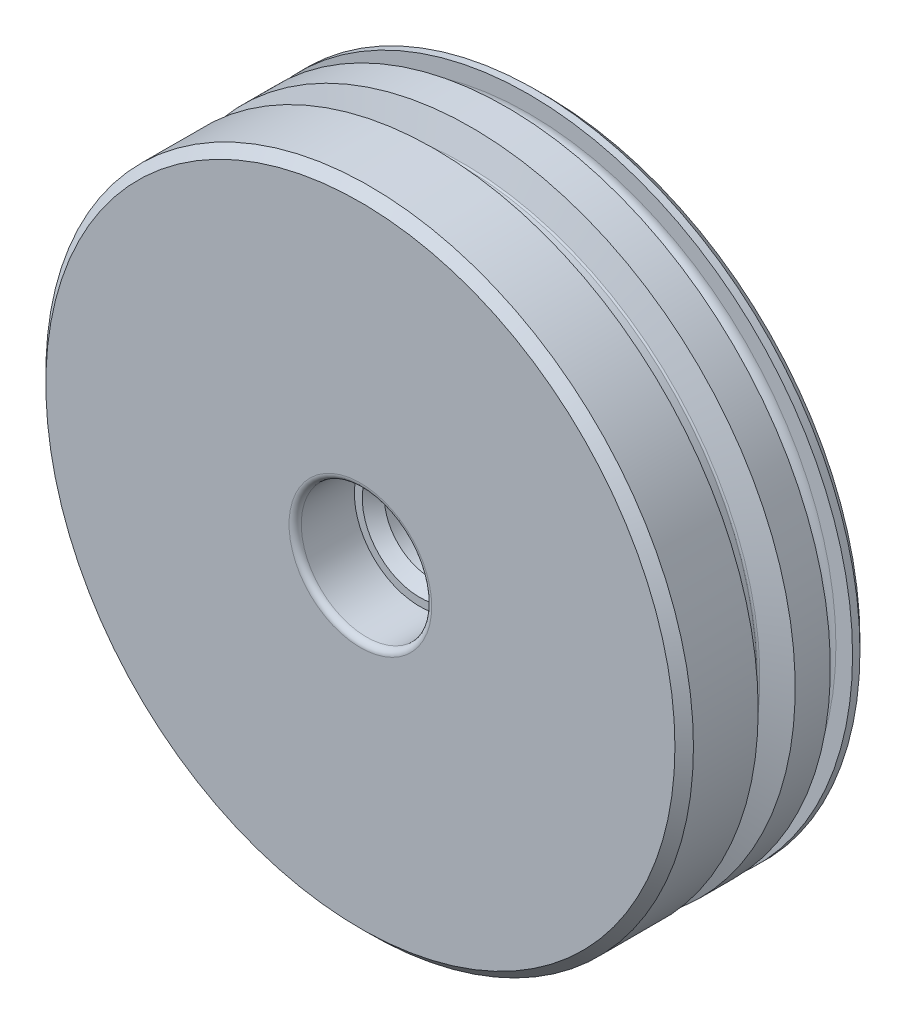
SolidWorks part; units mm, degrees
material "Delrin 2700 NC010, Low Viscosity Acetal Copolymer (SS)"
ref_plane "Front Plane" through (0, 0, 0) normal (0, 0, 1) x (1, 0, 0)
ref_plane "Top Plane" through (0, 0, 0) normal (0, 1, 0) x (1, 0, 0)
ref_plane "Right Plane" through (0, 0, 0) normal (1, 0, 0) x (0, 0, -1)
sketch "Sketch1" plane through (0, 0, 0) normal (0, 0, 1) x (1, 0, 0)
  circle A0 centre (0, 0) radius 17.5
  dimension "D1" = 35
extrude "Boss-Extrude1" add sketch "Sketch1" along normal blind 5 and the other way blind 5
sketch "Sketch3" plane through (0, 0, 0) normal (1, 0, 0) x (0, 0, -1)
  line L0 (0, 19.25) -> (0, -19.25) construction
  line L2 (-1, 17.5) -> (-0.5228, 16.0684)
  line L4 (-0.4279, 16) -> (0.4279, 16)
  line L5 (-1, 17.5) -> (1, 17.5)
  line L6 (0.5228, 16.0684) -> (1, 17.5)
  arc A0 (0.4279, 16) -> (0.5228, 16.0684) centre (0.4279, 16.1) ccw
  arc A1 (-0.4279, 16) -> (-0.5228, 16.0684) centre (-0.4279, 16.1) cw
  point P1 (0, 16)
  point P5 (0, 17.5)
  point P10 (0.5, 16)
  point P14 (-0.5, 16)
  dimension "D1" = 1
  dimension "D4" = 0.1
  dimension "D2" = 2
  dimension "D3" = 1.5
ref_axis "Axis1" through (0, 0, -0.35) along (0, 0, 1)
revolve "Cut-Revolve1" cut sketch "Sketch3" angle 360 about axis through (0, 0, -0.35) along (0, 0, 1)
sketch "Sketch2" plane through (0, 0, 5) normal (0, 0, 1) x (1, 0, 0)
  circle A0 centre (0, 0) radius 3.525
  dimension "D1" = 7.05
extrude "Cut-Extrude1" cut sketch "Sketch2" against normal blind 3.2
chamfer "Chamfer1" distance 0.5 angle 45 2 edges at (17.5, 0, 5) (17.5, 0, -5)
sketch "Sketch4" plane through (0, 0, 1.8) normal (0, 0, 1) x (1, 0, 0)
  circle A0 centre (0, 0) radius 2.5
  dimension "D1" = 5
extrude "Cut-Extrude2" cut sketch "Sketch4" against normal through all
ref_axis "Axis2" through (0, 19.25, 5) along (0, -1, 0)
chamfer "Chamfer2" distance 0.6 angle 45 1 edges at (2.5, 0, 1.8)
mirror "Mirror2" about plane through (0, 0, 0) normal (0, 0, 1) of "Chamfer2", "Cut-Extrude1"
ref_plane "Plane4" through (0, 17.5, 0) normal (0, 1, 0) x (1, 0, 0)
sketch "Sketch7" plane through (0, 0, 0) normal (1, 0, 0) x (0, 0, -1)
  line L5 (4.5, 17.5) -> (4.5, -17.5) construction
  line L7 (2.9, 16.6) -> (2.9, 17.5)
  line L8 (2.9, 17.5) -> (4.1, 17.5)
  line L9 (4.1, 17.5) -> (4.1, 16.6)
  line L10 (3.5, 16) -> (4.2963, 16) construction
  arc A0 (2.9, 16.6) -> (4.1, 16.6) centre (3.5, 16.6) ccw
  dimension "D1" = 1.2
  dimension "D3" = 1.5
  dimension "D2" = 1
revolve "Cut-Revolve3" cut sketch "Sketch7" angle 360 about axis through (0, 0, -0.35) along (0, 0, 1)
fillet "Fillet1" radius 0.33 2 edges at (3.525, 0, 5) (3.525, 0, -5)
sketch "Sketch9" plane through (0, 0, -5) normal (0, 0, -1) x (-1, 0, 0)
  line L0 (-4.4, 1.6) -> (-7.6, 1.6)
  line L1 (7.6, 1.6) -> (4.4, 1.6)
  line L2 (7.6, 1.6) -> (7.6, -1.6)
  line L3 (7.6, -1.6) -> (4.4, -1.6)
  line L4 (4.4, 1.6) -> (4.4, -1.6)
  line L5 (7.6, 1.6) -> (4.4, -1.6) construction
  line L6 (7.6, -1.6) -> (4.4, 1.6) construction
  line L7 (-4.4, 1.6) -> (-4.4, -1.6)
  line L8 (-4.4, -1.6) -> (-7.6, -1.6)
  line L9 (-7.6, 1.6) -> (-7.6, -1.6)
  line L10 (-4.4, 1.6) -> (-7.6, -1.6) construction
  line L11 (-4.4, -1.6) -> (-7.6, 1.6) construction
  line L13 (0, 0) -> (4.4, 0) construction
  line L14 (0, 0) -> (-4.4, 0) construction
  point P0 (6, 0)
  point P5 (-6, 0)
  dimension "D1" = 3.2
  dimension "D2" = 3.2
  dimension "D3" = 3.2
  dimension "D4" = 3.2
  dimension "D5" = 12
extrude "Cut-Extrude4" cut sketch "Sketch9" against normal blind 4
